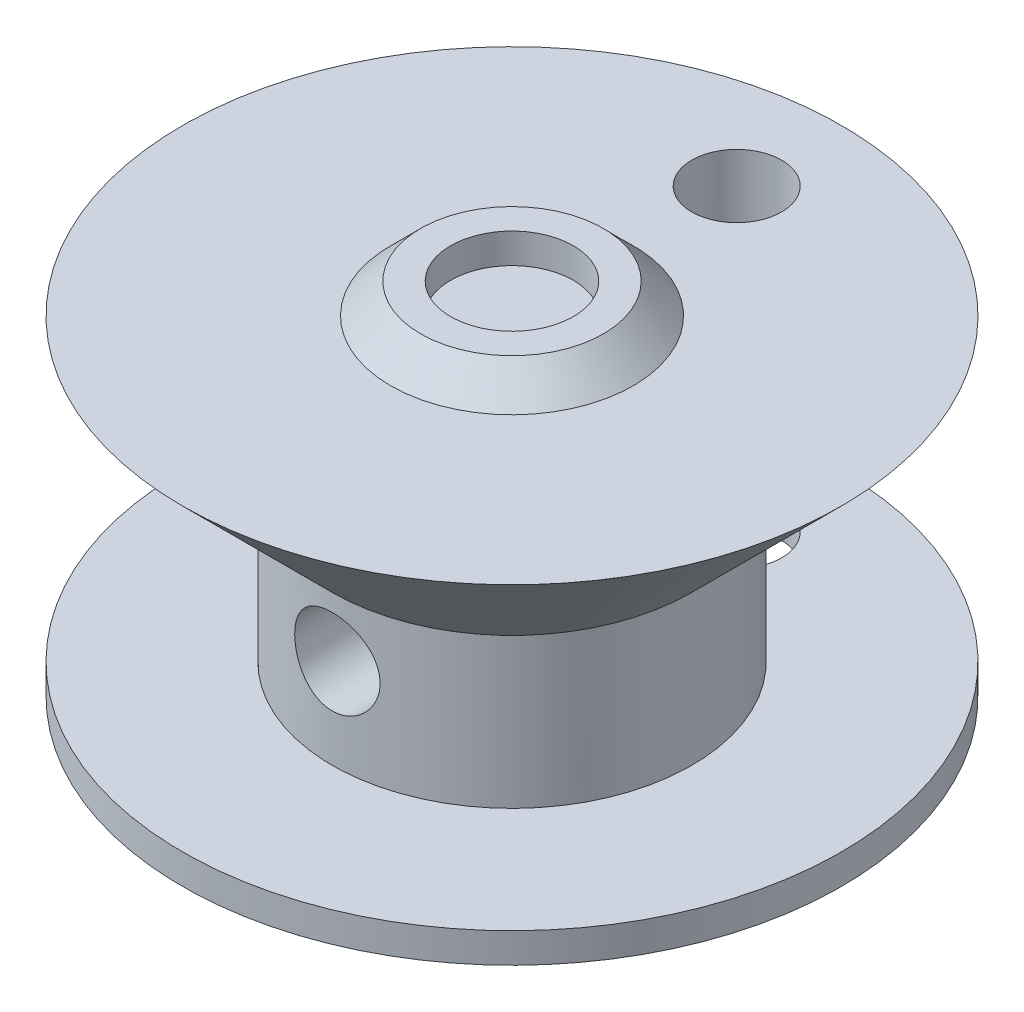
SolidWorks part; units mm, degrees
material "ABS"
ref_plane "Front Plane" through (0, 0, 0) normal (0, 0, 1) x (1, 0, 0)
ref_plane "Top Plane" through (0, 0, 0) normal (0, 1, 0) x (1, 0, 0)
ref_plane "Right Plane" through (0, 0, 0) normal (1, 0, 0) x (0, 0, -1)
sketch "Sketch1" plane through (0, 0, 0) normal (1, 0, 0) x (0, 0, -1)
  line L0 (0, 6) -> (-11, 6) construction
  line L1 (0, 0) -> (0, 18.3424) construction
  line L2 (-11, 6) -> (-11, -6) construction
  line L3 (-11, -6) -> (0, -6) construction
  line L4 (0, -6) -> (0, 6) construction
  line L5 (-11, 6) -> (-11, 5)
  line L7 (-6, 0) -> (-6, -5)
  line L9 (-11, -5) -> (-11, -6)
  line L10 (-11, -6) -> (0, -6) construction
  line L11 (0, -6) -> (0, 6) construction
  line L12 (0, 6) -> (-11, 6) construction
  line L13 (-11, 5) -> (-6, 0)
  line L14 (-6, 0) -> (-6, 6) construction
  line L15 (-11, -5) -> (-6, -5)
  line L16 (-11, 6) -> (-2, 6)
  line L17 (2, -6) -> (-2, -6) construction
  line L18 (2, -6) -> (2, 6) construction
  line L19 (2, 6) -> (-2, 6) construction
  line L20 (-2, -6) -> (-2, 6) construction
  line L21 (2, -6) -> (-2, 6) construction
  line L22 (2, 6) -> (-2, -6) construction
  line L23 (-2.05, 5) -> (2.05, 5) construction
  line L24 (-2.05, 5) -> (-2.05, 7) construction
  line L25 (-2.05, 7) -> (2.05, 7) construction
  line L26 (2.05, 5) -> (2.05, 7) construction
  line L27 (-2.05, 5) -> (2.05, 7) construction
  line L28 (-2.05, 7) -> (2.05, 5) construction
  line L30 (-2.05, 5) -> (0, 5)
  line L31 (0, 5) -> (0, -6) construction
  line L33 (-2, 2) -> (-2, -6)
  line L34 (-2, -6) -> (-11, -6)
  line L35 (-2, 2) -> (0, 4)
  line L36 (0, 4) -> (0, 5)
  line L37 (-2.05, 5) -> (-2.05, 6)
  line L38 (-2.05, 6) -> (-2, 6)
  point P3 (0, 0)
  point P16 (0, 0)
  dimension "D1" = 22
  dimension "D2" = 8
  dimension "D3" = 45
  dimension "D4" = 1
  dimension "D5" = 5
  dimension "D6" = 4
  dimension "D7" = 4
  dimension "D8" = 4.1
  dimension "D9" = 1
  dimension "D10" = 45
  dimension "D11" = 12
revolve "Spool Solid" add sketch "Sketch1" angle 360 about L1 region at (0, 0.7664, 5.0692)
sketch "Sketch2" plane through (0, -6, 0) normal (0, -1, 0) x (1, 0, 0)
  line L0 (1.3229, 1.5) -> (-1.3229, 1.5)
  circle A2 centre (0, 0) radius 2 construction
  circle A3 centre (0, 0) radius 2 construction
  arc A4 (1.3229, 1.5) -> (-1.3229, 1.5) centre (0, 0) ccw
  point P0 (0, -2)
  point P3 (0, 1.5)
  dimension "D1" = 3.5
extrude "Flat Grove Extrude" add sketch "Sketch2" against normal up to next
sketch "Sketch5" plane through (0, -5, 0) normal (0, 1, 0) x (1, 0, 0)
  line L0 (0, 6) -> (0, 11) construction
  circle A0 centre (0, 7.5) radius 1.5
  circle A1 centre (0, 0) radius 6 construction
  circle A2 centre (0, 0) radius 11 construction
  point P9 (0, 0)
  point P10 (0, 0)
  dimension "D1" = 3
extrude "Wire Hole Cut" cut sketch "Sketch5" against normal through all both and the other way through all
sketch "Sketch6" plane through (0, 0, 1.5) normal (0, 0, -1) x (-1, 0, 0)
  line L0 (0, -6) -> (0, 2) construction
  line L1 (1.3229, -6) -> (-1.3229, -6) construction
  circle A0 centre (0, -2) radius 1.425
  dimension "D2" = 2.85
  dimension "D1" = 8
extrude "Set Screw Cut" cut sketch "Sketch6" against normal through all
sketch "Sketch8" plane through (0, 6, 0) normal (0, 1, 0) x (1, 0, 0)
  circle A1 centre (0, 0) radius 11
  circle A4 centre (0, 0) radius 11 construction
  circle A6 centre (0, 0) radius 3.05
  circle A7 centre (0, 0) radius 3.05
  dimension "D1" = 1
extrude "Magnet Holder Trim" cut sketch "Sketch8" against normal blind 1
chamfer "Magnet Holder Chamfer" distance 1 angle 45 1 edges at (0, 5, 3.05)
sketch "Sketch9" plane through (0, -6, 0) normal (0, -1, 0) x (1, 0, 0)
  line L2 (1.3964, 1.7) -> (-1.3964, 1.7)
  line L3 (1.3964, 1.7) -> (-1.3964, 1.7)
  arc A2 (-1.3964, 1.7) -> (1.3964, 1.7) centre (0, 0) ccw
  arc A3 (-1.3964, 1.7) -> (1.3964, 1.7) centre (0, 0) ccw
  dimension "D1" = 0.2
extrude "Axle Tolerance Cut" cut sketch "Sketch9" against normal up to vertex (8 mm away) up to point (1.3229, 2, 1.5)
